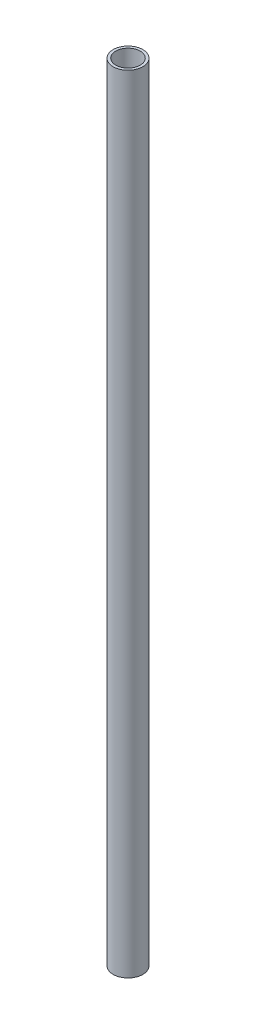
SolidWorks part; units mm, degrees
ref_plane "Спереди" through (0, 0, 0) normal (0, 0, 1) x (1, 0, 0)
ref_plane "Сверху" through (0, 0, 0) normal (0, 1, 0) x (1, 0, 0)
ref_plane "Справа" through (0, 0, 0) normal (1, 0, 0) x (0, 0, -1)
sketch "Эскиз1" plane through (0, 0, 0) normal (0, 1, 0) x (1, 0, 0)
  circle A0 centre (0, 0) radius 17
extrude "Вытянуть-Тонкостенный1" add sketch "Эскиз1" along normal blind 900 thin thin type one direction reverse wall 3
